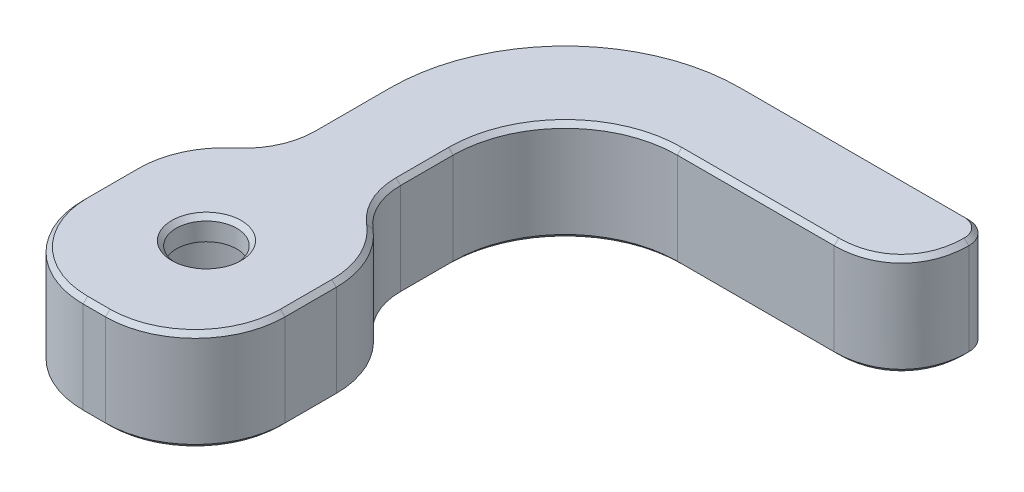
SolidWorks part; units mm, degrees
ref_plane "前视基准面" through (0, 0, 0) normal (0, 0, 1) x (1, 0, 0)
ref_plane "上视基准面" through (0, 0, 0) normal (0, 1, 0) x (1, 0, 0)
ref_plane "右视基准面" through (0, 0, 0) normal (1, 0, 0) x (0, 0, -1)
other "Configuration Table"
sketch "草图1" plane through (0, 0, 0) normal (0, 1, 0) x (1, 0, 0)
  line L0 (6.5, 10) -> (9, 10)
  line L1 (0, 0) -> (9, 0)
  line L2 (0, 0) -> (0, 10)
  line L3 (0, 10) -> (2.5, 10)
  line L4 (9, 0) -> (9, 10)
  line L6 (2.5, 10) -> (2.5, 23)
  line L7 (2.5, 23) -> (6.5, 23)
  line L8 (6.5, 10) -> (6.5, 23)
  circle A0 centre (4.5, 5) radius 2.5
  point P7 (4.5, 0)
  point P13 (4.5, 23)
  dimension "D1" = 5
  dimension "D3" = 0
  dimension "D4" = 5
  dimension "D2" = 9
  dimension "D5" = 10
  dimension "D6" = 4
  dimension "D7" = 2.5
  dimension "D8" = 13
extrude "凸台-拉伸1" add sketch "草图1" along normal blind 4.5
sketch "草图3" plane through (0, 4.5, 0) normal (0, 1, 0) x (1, 0, 0)
  circle A0 centre (4.5, 5) radius 2.5
  circle A1 centre (4.5, 5) radius 1.35
  circle A2 centre (4.5, 5) radius 2.5 construction
  dimension "D1" = 2.7
  dimension "D2" = 0
extrude "凸台-拉伸3" add sketch "草图3" against normal blind 1
sketch "草图4" plane through (6.5, 0, 0) normal (1, 0, 0) x (0, 0, -1)
  line L0 (10, 0) -> (23, 0) construction
  line L1 (23, 4.5) -> (19, 4.5)
  line L2 (23, 4.5) -> (23, 0)
  line L3 (23, 0) -> (19, 0)
  line L4 (19, 4.5) -> (19, 0)
  dimension "D1" = 4
extrude "凸台-拉伸4" add sketch "草图4" along normal blind 15
fillet "圆角1" radius 3 1 edges at (21.5, 2.25, -19) conic rho 0.45
fillet "圆角3" radius 5 1 edges at (6.5, 2.25, -19)
fillet "圆角4" radius 8 1 edges at (2.5, 2.25, -23)
fillet "圆角5" radius 4 4 edges at (9, 2.25, 0) (0, 2.25, 0) (9, 2.25, -10) (0, 2.25, -10)
fillet "圆角6" radius 3 2 edges at (6.5, 2.25, -10) (2.5, 2.25, -10)
fillet "圆角7" radius 1 1 edges at (21.5, 2.25, -23)
chamfer "倒角3" distance 0.2 angle 45 36 edges at (4.5, 4.5, -3.65) (7.9645, 4.5, -17.5355) (6.5, 4.5, -12.8269) (6.781, 4.5, -10.3861) (8.6253, 4.5, -7.9822) (9, 4.5, -5.146) (7.8284, 4.5, -1.1716) (4.5, 4.5, 0) (1.1716, 4.5, -1.1716) (0, 4.5, -5.146) (0.3747, 4.5, -7.9822) (2.219, 4.5, -10.3861) (2.5, 4.5, -13.3269) (4.8431, 4.5, -20.6569) (15.5, 4.5, -23) (4.5, 0, -2.5) (4.8431, 0, -20.6569) (2.5, 0, -13.3269) (2.219, 0, -10.3861) (0.3747, 0, -7.9822) (0, 0, -5.146) (1.1716, 0, -1.1716) (4.5, 0, 0) (7.8284, 0, -1.1716) (9, 0, -5.146) (8.6253, 0, -7.9822) (6.781, 0, -10.3861) (6.5, 0, -12.8269) (7.9645, 0, -17.5355) (15.5, 0, -23)
fillet "圆角8" radius 2 1 edges at (4.5, 0.2, -7.5)
